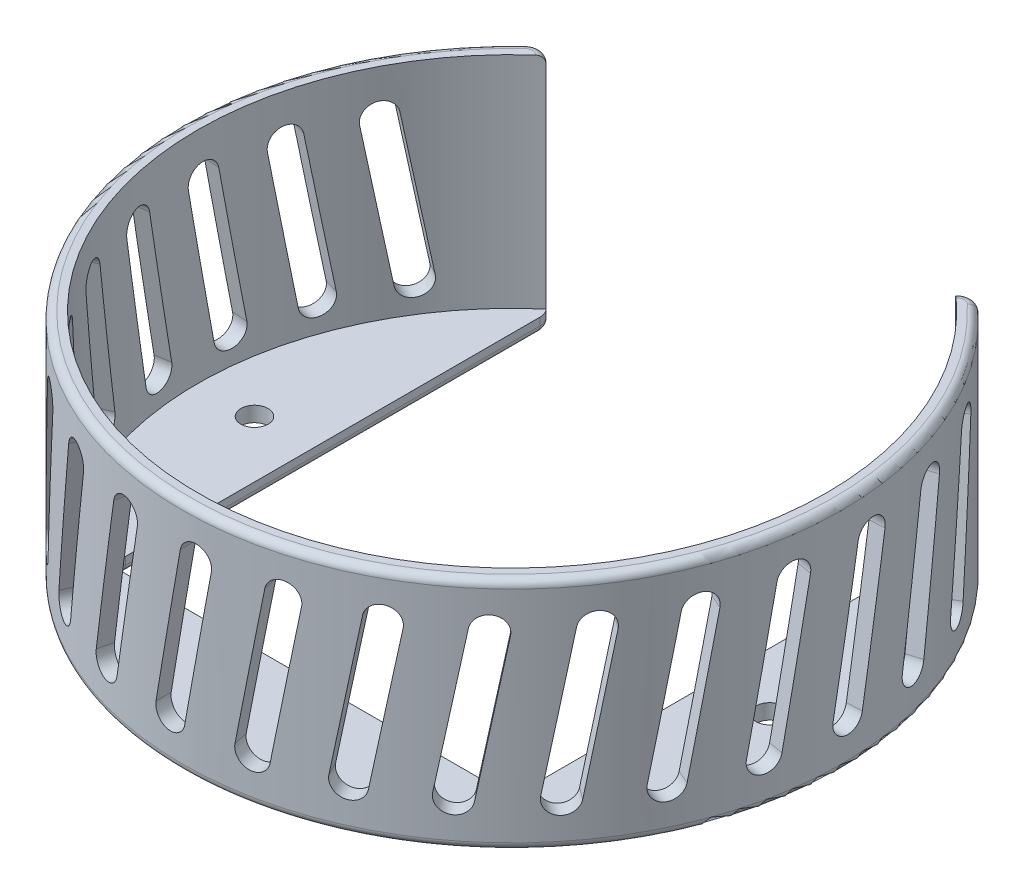
SolidWorks part; units mm, degrees
ref_plane "Front Plane" through (0, 0, 0) normal (0, 0, 1) x (1, 0, 0)
ref_plane "Top Plane" through (0, 0, 0) normal (0, 1, 0) x (1, 0, 0)
ref_plane "Right Plane" through (0, 0, 0) normal (1, 0, 0) x (0, 0, -1)
sketch "Sketch1" plane through (0, 0, 0) normal (0, 1, 0) x (1, 0, 0)
  circle A0 centre (0, 0) radius 43.5
  dimension "D1" = 87
extrude "Boss-Extrude1" add sketch "Sketch1" along normal blind 2
sketch "Sketch2" plane through (0, 2, 0) normal (0, 1, 0) x (1, 0, 0)
  circle A0 centre (0, 0) radius 43.5 construction
  circle A1 centre (0, 0) radius 43.5
  circle A2 centre (0, 0) radius 41.5
  dimension "D1" = 2
extrude "Boss-Extrude2" add sketch "Sketch2" along normal blind 29
sketch "Sketch4" plane through (0, 0, 0) normal (0, -1, 0) x (1, 0, 0)
  circle A0 centre (34, 0) radius 1.8
  circle A1 centre (17, -29.4449) radius 1.8
  circle A2 centre (-17, -29.4449) radius 1.8
  circle A3 centre (-34, 0) radius 1.8
  circle A4 centre (-17, 29.4449) radius 1.8
  circle A5 centre (17, 29.4449) radius 1.8
  point P2 (-1.0878, 13.8307)
  point P16 (0, 0)
  dimension "D1" = 3.6
  dimension "D2" = 34
  dimension "D3" = 6
extrude "Cut-Extrude2" cut sketch "Sketch4" against normal through all
sketch "Sketch5" plane through (0, 0, 0) normal (0, -1, 0) x (1, 0, 0)
  line L0 (-26.5, 26.5036) -> (26.5, 26.5036)
  line L1 (26.5, 26.5036) -> (26.5, -34.4964)
  line L2 (-26.5, 26.5036) -> (-26.5, -34.4964)
  circle A0 centre (0, 0) radius 43.5 construction
  arc A1 (-26.5, -34.4964) -> (26.5, -34.4964) centre (0, 0) ccw
  point P2 (0, 26.5036)
  point P9 (-26.5, -34.4964)
  point P10 (0, 0)
  dimension "D1" = 53
  dimension "D2" = 61
extrude "Cut-Extrude3" cut sketch "Sketch5" against normal through all
ref_plane "Plane1" through (0, 0, 43.5) normal (0, 0, 1) x (1, 0, 0)
sketch "Sketch6" plane through (0, 0, 43.5) normal (0, 0, 1) x (1, 0, 0)
  line L0 (-1.6805, 5.9696) -> (1.6805, 25.0304) construction
  line L1 (-3.6501, 6.3169) -> (-0.2892, 25.3777)
  line L2 (0.2892, 5.6223) -> (3.6501, 24.6831)
  line L3 (-43.5, 0) -> (43.5, 0) construction
  line L4 (43.5, 31) -> (-43.5, 31) construction
  arc A0 (-3.6501, 6.3169) -> (0.2892, 5.6223) centre (-1.6805, 5.9696) ccw
  arc A1 (3.6501, 24.6831) -> (-0.2892, 25.3777) centre (1.6805, 25.0304) ccw
  point P2 (0, 15.5)
  point P7 (0, 0)
  point P11 (2.0278, 27)
  point P14 (-1.8026, 3.5845)
  point P15 (-2.0278, 4)
  dimension "D3" = 4
  dimension "D1" = 80
  dimension "D2" = 4
  dimension "D4" = 4
extrude "Cut-Extrude4" cut sketch "Sketch6" against normal blind 10
pattern_circular "CirPattern1" count 10 every 13.333 about axis through (0, 0, 0) along (0, 1, 0) of "Cut-Extrude4" other way count 10
fillet "Fillet1" radius 2 4 edges at (-26.5, 15.5, -34.4964) (26.5, 15.5, -34.4964) (26.5, 1, 26.5036) (-26.5, 1, 26.5036)
fillet "Fillet2" radius 1 11 edges at (-27.7085, 0, -32.0029) (-26.5, 0, -2.8313) (-25.9142, 0, 25.9178) (0, 0, 26.5036) (25.9142, 0, 25.9178) (26.5, 0, -2.8313) (27.7085, 0, -32.0029) (0, 0, 43.5) (-28.4191, 31, -32.1646) (28.4191, 31, -32.1646) (0, 31, 43.5)
